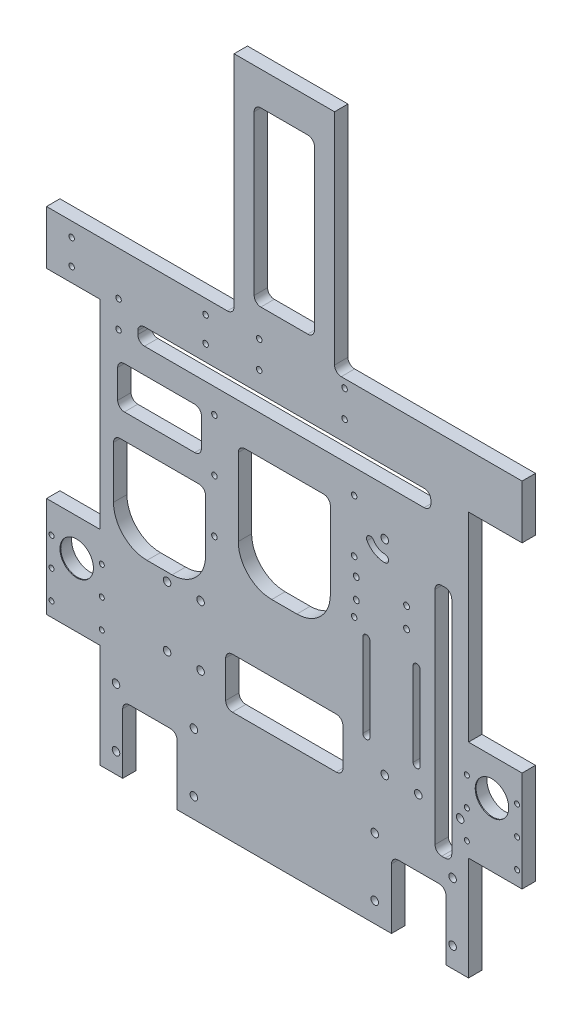
SolidWorks part; units mm, degrees
ref_plane "Front" through (0, 0, 0) normal (0, 0, 1) x (1, 0, 0)
ref_plane "Top" through (0, 0, 0) normal (0, 1, 0) x (1, 0, 0)
ref_plane "Right" through (0, 0, 0) normal (1, 0, 0) x (0, 0, -1)
sketch "Esquisse1" plane through (0, 0, 0) normal (0, 0, 1) x (1, 0, 0)
  line L1 (0, 0) -> (220, 0)
  line L2 (0, 0) -> (0, 285)
  line L3 (0, 285) -> (220, 285)
  line L4 (220, 0) -> (220, 285)
  dimension "D1" = 220
  dimension "D2" = 285
extrude "Boss.-Extru.1" add sketch "Esquisse1" along normal blind 8
sketch "Esquisse2" plane through (0, 0, 0) normal (0, -1, 0) x (1, 0, 0)
  line L0 (0, 4) -> (220, 4) construction
  line L1 (0, 8) -> (0, 0) construction
  line L2 (220, 8) -> (220, 0) construction
  line L3 (110, 4) -> (110, 28.0559) construction
  circle A0 centre (110, 4) radius 2
  circle A1 centre (213, 4) radius 2
  circle A2 centre (7, 4) radius 2
  dimension "D1" = 4
  dimension "D2" = 103
extrude "Enlèv. mat.-Extru.1" cut sketch "Esquisse2" against normal blind 8
sketch "Esquisse3" plane through (0, 0, 8) normal (0, 0, 1) x (1, 0, 0)
  line L0 (110, 0) -> (110, 285) construction
  line L1 (0, 0) -> (220, 0) construction
  line L2 (220, 285) -> (0, 285) construction
  line L3 (82.5, 207) -> (137.5, 207)
  line L4 (137.5, 207) -> (137.5, 137)
  line L5 (137.5, 137) -> (82.5, 137)
  line L6 (82.5, 207) -> (82.5, 137)
  line L8 (8, 175) -> (63, 175)
  line L9 (8, 175) -> (8, 120)
  line L10 (8, 120) -> (63, 120)
  line L11 (63, 175) -> (63, 120)
  line L12 (200, 55) -> (210, 55)
  line L13 (200, 55) -> (200, 195)
  line L14 (200, 195) -> (210, 195)
  line L15 (210, 55) -> (210, 195)
  point P11 (110, 137)
  point P12 (110, 207)
  dimension "D1" = 70
  dimension "D2" = 55
  dimension "D3" = 137
  dimension "D4" = 55
  dimension "D5" = 47
  dimension "D6" = 55
  dimension "D7" = 120
  dimension "D8" = 140
  dimension "D9" = 55
  dimension "D10" = 90
  dimension "D11" = 10
extrude "Enlèv. mat.-Extru.2" cut sketch "Esquisse3" against normal through all both and the other way through all
sketch "Esquisse5" plane through (0, 0, 8) normal (0, 0, 1) x (1, 0, 0)
  line L0 (110, 230) -> (110, 0) construction
  line L1 (22.5, 240) -> (197.5, 240)
  line L2 (22.5, 240) -> (22.5, 230)
  line L3 (22.5, 230) -> (197.5, 230)
  line L4 (197.5, 240) -> (197.5, 230)
  line L5 (0, 0) -> (220, 0) construction
  dimension "D1" = 175
  dimension "D2" = 10
  dimension "D3" = 230
extrude "Enlèv. mat.-Extru.3" cut sketch "Esquisse5" against normal through all both and the other way through all
sketch "Esquisse6" plane through (0, 0, 8) normal (0, 0, 1) x (1, 0, 0)
  line L0 (170, 80) -> (190, 80) construction
  line L1 (0, 0) -> (220, 0) construction
  line L2 (137.5, 137) -> (82.5, 137) construction
  line L3 (215, 80) -> (190, 80) construction
  line L4 (168, 191.6799) -> (168, 168) construction
  line L5 (186.4274, 168) -> (149.5726, 168) construction
  line L6 (0, 285) -> (0, 0) construction
  circle A0 centre (190, 80) radius 2.25
  circle A1 centre (170, 80) radius 2.25
  circle A2 centre (215, 80) radius 2.25
  circle A3 centre (153, 174) radius 1.75
  circle A4 centre (183, 174) radius 1.75
  circle A5 centre (183, 162) radius 1.75
  circle A6 centre (153, 162) radius 1.75
  point P8 (110, 137)
  dimension "D1" = 4.5
  dimension "D3" = 80
  dimension "D6" = 30
  dimension "D7" = 12
  dimension "D8" = 3.5
  dimension "D2" = 20
  dimension "D4" = 60
  dimension "D5" = 25
  dimension "D9" = 168
  dimension "D10" = 168
extrude "Enlèv. mat.-Extru.4" cut sketch "Esquisse6" against normal through all both and the other way through all
sketch "Esquisse7" plane through (0, 0, 8) normal (0, 0, 1) x (1, 0, 0)
  line L0 (110, 0) -> (110, 285) construction
  line L1 (0, 0) -> (220, 0) construction
  line L2 (220, 285) -> (0, 285) construction
  line L3 (68.285, 184) -> (68.285, 215.4) construction
  line L4 (68.285, 184) -> (110, 184) construction
  line L5 (151.715, 184) -> (151.715, 215.4) construction
  line L6 (95, 268) -> (120.5, 268) construction
  line L7 (120.5, 268) -> (120.5, 260) construction
  line L8 (120.5, 260) -> (137.9818, 260) construction
  line L9 (95, 252) -> (120.5, 252) construction
  line L10 (22.5, 240) -> (197.5, 240) construction
  circle A0 centre (68.285, 215.4) radius 1.65
  circle A1 centre (68.285, 184) radius 1.65
  circle A2 centre (68.285, 152.6) radius 1.65
  circle A3 centre (151.715, 152.6) radius 1.65
  circle A4 centre (151.715, 184) radius 1.65
  circle A5 centre (151.715, 215.4) radius 1.65
  circle A6 centre (95, 268) radius 1.65
  circle A7 centre (146, 268) radius 1.65
  circle A8 centre (146, 252) radius 1.65
  circle A9 centre (95, 252) radius 1.65
  dimension "D1" = 31.4
  dimension "D2" = 3.3
  dimension "D5" = 16
  dimension "D6" = 51
  dimension "D9" = 3.3
  dimension "D7" = 15
  dimension "D3" = 83.43
  dimension "D4" = 184
  dimension "D8" = 20
extrude "Enlèv. mat.-Extru.5" cut sketch "Esquisse7" against normal through all both and the other way through all
sketch "Esquisse8" plane through (0, 0, 8) normal (0, 0, 1) x (1, 0, 0)
  line L0 (110, 0) -> (110, 285) construction
  line L1 (0, 0) -> (220, 0) construction
  line L2 (220, 285) -> (0, 285) construction
  line L3 (174, 0) -> (174, 40)
  line L4 (13.5, 0) -> (46, 0)
  line L5 (13.5, 0) -> (13.5, 40)
  line L6 (13.5, 40) -> (46, 40)
  line L7 (46, 0) -> (46, 40)
  line L8 (206.5, 40) -> (174, 40)
  line L9 (206.5, 0) -> (206.5, 40)
  line L10 (206.5, 0) -> (174, 0)
  dimension "D1" = 128
  dimension "D2" = 32.5
  dimension "D3" = 40
extrude "Enlèv. mat.-Extru.6" cut sketch "Esquisse8" against normal through all both and the other way through all
fillet "Congé1" radius 20 4 edges at (137.5, 137, 4) (82.5, 137, 4) (63, 120, 4) (8, 120, 4)
sketch "Esquisse9" plane through (0, 0, 8) normal (0, 0, 1) x (1, 0, 0)
  line L0 (189, 145) -> (189, 95) construction
  line L1 (191.1, 145) -> (191.1, 95)
  line L2 (186.9, 145) -> (186.9, 95)
  line L3 (189, 120) -> (159, 120) construction
  line L4 (174, 120) -> (174, 121.5076) construction
  line L5 (159, 95) -> (159, 145) construction
  line L6 (156.9, 95) -> (156.9, 145)
  line L7 (161.1, 95) -> (161.1, 145)
  line L9 (210, 55) -> (200, 55) construction
  line L10 (200, 55) -> (200, 195) construction
  arc A0 (191.1, 145) -> (186.9, 145) centre (189, 145) ccw
  arc A1 (186.9, 95) -> (191.1, 95) centre (189, 95) ccw
  arc A2 (156.9, 95) -> (161.1, 95) centre (159, 95) ccw
  arc A3 (161.1, 145) -> (156.9, 145) centre (159, 145) ccw
  point P2 (189, 120)
  point P13 (159, 120)
  dimension "D1" = 4.2
  dimension "D2" = 30
  dimension "D3" = 11
  dimension "D4" = 40
  dimension "D5" = 50
extrude "Enlèv. mat.-Extru.7" cut sketch "Esquisse9" against normal through all both and the other way through all
sketch "Esquisse10" plane through (0, 0, 8) normal (0, 0, 1) x (1, 0, 0)
  line L0 (9.5, 0) -> (9.5, 52.9697) construction
  line L1 (0, 0) -> (13.5, 0) construction
  line L2 (0, 285) -> (0, 0) construction
  line L3 (110, 0) -> (110, 48.9194) construction
  line L4 (46, 0) -> (174, 0) construction
  line L5 (32.75, 0) -> (32.75, 52.9697) construction
  circle A0 centre (9.5, 12) radius 2.25
  circle A1 centre (9.5, 47) radius 2.25
  circle A2 centre (210.5, 47) radius 2.25
  circle A3 centre (210.5, 12) radius 2.25
  circle A4 centre (56, 47) radius 2.25
  circle A5 centre (56, 12) radius 2.25
  circle A6 centre (164, 12) radius 2.25
  circle A7 centre (164, 47) radius 2.25
  dimension "D2" = 4.5
  dimension "D3" = 35
  dimension "D4" = 12
  dimension "D5" = 46.5
  dimension "D1" = 9.5
extrude "Enlèv. mat.-Extru.8" cut sketch "Esquisse10" against normal through all both and the other way through all
sketch "Esquisse11" plane through (0, 0, 8) normal (0, 0, 1) x (1, 0, 0)
  line L0 (110, 67) -> (110, 0) construction
  line L1 (75, 97) -> (145, 97)
  line L2 (75, 97) -> (75, 67)
  line L3 (75, 67) -> (145, 67)
  line L4 (145, 97) -> (145, 67)
  line L5 (46, 0) -> (174, 0) construction
  dimension "D1" = 70
  dimension "D2" = 30
  dimension "D3" = 67
extrude "Enlèv. mat.-Extru.9" cut sketch "Esquisse11" against normal through all both and the other way through all
sketch "Esquisse12" plane through (0, 0, 8) normal (0, 0, 1) x (1, 0, 0)
  line L0 (220, 0) -> (220, 285) construction
  line L1 (46, 0) -> (174, 0) construction
  line L2 (170, 202) -> (161.3397, 197) construction
  line L3 (170, 192) -> (170, 202) construction
  circle A0 centre (170, 202) radius 2.25
  arc A1 (161.3397, 197) -> (170, 192) centre (170, 202) ccw construction
  arc A2 (159.3912, 195.875) -> (170, 189.75) centre (170, 202) ccw
  arc A3 (163.2883, 198.125) -> (170, 194.25) centre (170, 202) ccw
  arc A4 (163.2883, 198.125) -> (159.3912, 195.875) centre (161.3397, 197) ccw
  arc A5 (170, 189.75) -> (170, 194.25) centre (170, 192) ccw
  point P9 (165, 193.3397)
  dimension "D1" = 4.5
  dimension "D2" = 50
  dimension "D3" = 202
  dimension "D4" = 4.5
  dimension "D5" = 10
  dimension "D6" = 60
extrude "Enlèv. mat.-Extru.10" cut sketch "Esquisse12" against normal through all both and the other way through all
sketch "Esquisse13" plane through (0, 0, 8) normal (0, 0, 1) x (1, 0, 0)
  line L0 (50, 123.132) -> (50, 97) construction
  line L1 (50, 97) -> (30.3926, 97) construction
  line L2 (46, 0) -> (174, 0) construction
  line L3 (0, 285) -> (0, 0) construction
  circle A0 centre (40, 115) radius 2.25
  circle A1 centre (60, 115) radius 2.25
  circle A2 centre (60, 79) radius 2.25
  circle A3 centre (40, 79) radius 2.25
  dimension "D1" = 36
  dimension "D2" = 20
  dimension "D3" = 4.5
  dimension "D4" = 97
  dimension "D5" = 40
extrude "Enlèv. mat.-Extru.11" cut sketch "Esquisse13" against normal through all both and the other way through all
sketch "Esquisse14" plane through (0, 0, 8) normal (0, 0, 1) x (1, 0, 0)
  line L0 (110, 0) -> (110, 159.9943) construction
  line L1 (0, 285) -> (80, 285)
  line L2 (0, 285) -> (0, 273)
  line L3 (0, 273) -> (80, 273)
  line L4 (80, 285) -> (80, 273)
  line L5 (46, 0) -> (174, 0) construction
  line L6 (140, 285) -> (140, 273)
  line L7 (220, 273) -> (140, 273)
  line L8 (220, 285) -> (220, 273)
  line L9 (220, 285) -> (140, 285)
  dimension "D1" = 12
  dimension "D2" = 80
extrude "Enlèv. mat.-Extru.12" cut sketch "Esquisse14" against normal through all both and the other way through all
sketch "Esquisse15" plane through (0, 0, 8) normal (0, 0, 1) x (1, 0, 0)
  line L0 (140, 285) -> (80, 285) construction
  line L1 (80, 285) -> (140, 285)
  line L2 (80, 285) -> (80, 408)
  line L3 (80, 408) -> (140, 408)
  line L4 (140, 285) -> (140, 408)
  line L5 (110, 408) -> (110, 0) construction
  line L6 (46, 0) -> (174, 0) construction
  dimension "D1" = 60
  dimension "D2" = 123
extrude "Boss.-Extru.2" add sketch "Esquisse15" against normal up to vertex (8 mm away) up to point (13.5, 0, 0)
sketch "Esquisse16" plane through (0, 0, 8) normal (0, 0, 1) x (1, 0, 0)
  line L0 (110, 388) -> (110, 408) construction
  line L1 (92, 285) -> (128, 285)
  line L2 (92, 285) -> (92, 388)
  line L3 (92, 388) -> (128, 388)
  line L4 (128, 285) -> (128, 388)
  line L5 (140, 408) -> (80, 408) construction
  line L6 (140, 273) -> (140, 408) construction
  line L7 (80, 273) -> (0, 273) construction
  dimension "D1" = 12
  dimension "D2" = 20
  dimension "D3" = 12
extrude "Enlèv. mat.-Extru.13" cut sketch "Esquisse16" against normal through all both and the other way through all
sketch "Esquisse17" plane through (0, 0, 8) normal (0, 0, 1) x (1, 0, 0)
  line L0 (110, 0) -> (110, -39.2027) construction
  line L1 (220, 273) -> (252, 273)
  line L2 (220, 273) -> (220, 241)
  line L3 (220, 241) -> (252, 241)
  line L4 (252, 273) -> (252, 241)
  line L5 (46, 0) -> (174, 0) construction
  line L6 (-32, 273) -> (-32, 241)
  line L7 (0, 241) -> (-32, 241)
  line L8 (0, 273) -> (0, 241)
  line L9 (0, 273) -> (-32, 273)
  line L10 (0, 273) -> (0, 0) construction
  line L11 (0, 62) -> (-32, 62)
  line L12 (0, 62) -> (0, 122)
  line L13 (0, 122) -> (-32, 122)
  line L14 (-32, 62) -> (-32, 122)
  line L15 (252, 62) -> (252, 122)
  line L16 (220, 122) -> (252, 122)
  line L17 (220, 62) -> (220, 122)
  line L18 (220, 62) -> (252, 62)
  dimension "D1" = 32
  dimension "D2" = 32
  dimension "D3" = 60
  dimension "D4" = 62
extrude "Boss.-Extru.3" add sketch "Esquisse17" against normal up to vertex (8 mm away) up to point (140, 273, 0)
sketch "Esquisse18" plane through (0, 0, 8) normal (0, 0, 1) x (1, 0, 0)
  line L0 (35.5, 190) -> (35.5, 175) construction
  line L1 (10.5, 190) -> (60.5, 190)
  line L2 (10.5, 190) -> (10.5, 215)
  line L3 (10.5, 215) -> (60.5, 215)
  line L4 (60.5, 190) -> (60.5, 215)
  line L5 (8, 175) -> (63, 175) construction
  dimension "D1" = 25
  dimension "D2" = 50
  dimension "D3" = 15
extrude "Enlèv. mat.-Extru.14" cut sketch "Esquisse18" against normal through all both and the other way through all
fillet "Congé2" radius 4 30 edges at (137.5, 207, 4) (82.5, 207, 4) (197.5, 230, 4) (197.5, 240, 4) (22.5, 240, 4) (22.5, 230, 4) (63, 175, 4) (8, 175, 4) (200, 195, 4) (210, 195, 4) (210, 55, 4) (200, 55, 4) (206.5, 40, 4) (174, 40, 4) (46, 40, 4) (13.5, 40, 4) (75, 67, 4) (145, 67, 4) (145, 97, 4) (75, 97, 4) (92, 388, 4) (128, 388, 4) (128, 285, 4) (92, 285, 4) (140, 273, 4) (80, 273, 4) (10.5, 215, 4) (60.5, 215, 4) (60.5, 190, 4) (10.5, 190, 4)
sketch "Esquisse19" plane through (0, 0, 8) normal (0, 0, 1) x (1, 0, 0)
  line L0 (-32, 257) -> (54.3473, 257) construction
  line L1 (-32, 273) -> (-32, 241) construction
  line L2 (23, 257) -> (23, 269.1) construction
  line L3 (11, 230.8) -> (11, 246.8) construction
  circle A0 centre (-17, 264.5) radius 1.65
  circle A1 centre (-17, 249.5) radius 1.65
  circle A2 centre (63, 249.5) radius 1.65
  circle A3 centre (63, 264.5) radius 1.65
  circle A4 centre (11, 246.8) radius 1.65
  circle A5 centre (11, 230.8) radius 1.65
  dimension "D2" = 80
  dimension "D3" = 3.3
  dimension "D5" = 28
  dimension "D6" = 16
  dimension "D7" = 10.2
  dimension "D1" = 15
  dimension "D4" = 55
extrude "Enlèv. mat.-Extru.15" cut sketch "Esquisse19" against normal through all both and the other way through all
sketch "Esquisse20" plane through (0, 0, 0) normal (0, 0, 1) x (1, 0, 0)
  line L0 (-32, 100) -> (-14, 100) construction
  line L2 (110, 0) -> (110, 74.504) construction
  line L3 (46, 0) -> (174, 0) construction
  line L4 (252, 100) -> (234, 100) construction
  line L5 (-32, 122) -> (-32, 62) construction
  circle A0 centre (-14, 100) radius 11.025
  circle A1 centre (234, 100) radius 11.025
  dimension "D1" = 22.05
  dimension "D3" = 100
  dimension "D2" = 18
extrude "Enlèv. mat.-Extru.16" cut sketch "Esquisse20" along normal blind 7.5
sketch "Esquisse21" plane through (0, 0, 7.5) normal (0, 0, -1) x (-1, 0, 0)
  line L0 (-110, 0) -> (-110, 78) construction
  line L1 (-46, 0) -> (-174, 0) construction
  circle A0 centre (14, 100) radius 10
  circle A1 centre (-234, 100) radius 10
  dimension "D1" = 20
extrude "Enlèv. mat.-Extru.17" cut sketch "Esquisse21" against normal through all both and the other way through all
sketch "Esquisse22" plane through (0, 0, 8) normal (0, 0, 1) x (1, 0, 0)
  line L0 (-14, 104.5) -> (-14, 70.5) construction
  line L1 (-14, 70.5) -> (-29, 70.5) construction
  line L2 (-14, 87.5) -> (-29, 87.5) construction
  line L3 (-14, 104.5) -> (-14, 110) construction
  line L4 (-29, 70.5) -> (-29, 87.5) construction
  line L5 (-14, 110) -> (-4, 100) construction
  line L6 (-24, 100) -> (-14, 110) construction
  line L7 (-24, 100) -> (-4, 100) construction
  line L8 (110, 0) -> (110, 176.4772) construction
  line L9 (46, 0) -> (174, 0) construction
  line L10 (244, 100) -> (224, 100) construction
  line L11 (244, 100) -> (234, 110) construction
  line L12 (234, 110) -> (224, 100) construction
  line L13 (249, 70.5) -> (249, 87.5) construction
  line L14 (234, 104.5) -> (234, 110) construction
  line L15 (234, 87.5) -> (249, 87.5) construction
  line L16 (234, 70.5) -> (249, 70.5) construction
  line L17 (234, 104.5) -> (234, 70.5) construction
  circle A0 centre (-29, 70.5) radius 1.5
  circle A1 centre (-29, 87.5) radius 1.5
  circle A2 centre (-29, 104.5) radius 1.5
  circle A3 centre (1, 104.5) radius 1.5
  circle A4 centre (1, 87.5) radius 1.5
  circle A5 centre (1, 70.5) radius 1.5
  circle A7 centre (-14, 100) radius 10 construction
  circle A8 centre (219, 70.5) radius 1.5
  circle A9 centre (219, 87.5) radius 1.5
  circle A10 centre (219, 104.5) radius 1.5
  circle A11 centre (249, 104.5) radius 1.5
  circle A12 centre (249, 87.5) radius 1.5
  circle A13 centre (249, 70.5) radius 1.5
  dimension "D1" = 3
  dimension "D2" = 30
  dimension "D3" = 17
  dimension "D4" = 12.5
extrude "Enlèv. mat.-Extru.18" cut sketch "Esquisse22" against normal through all both and the other way through all
